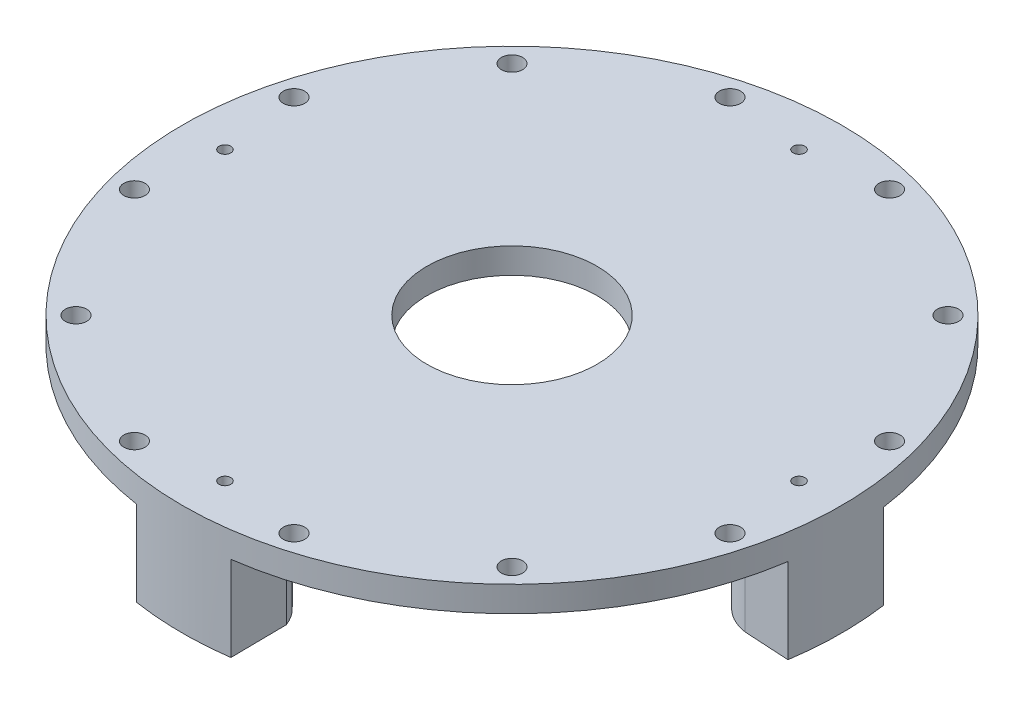
SolidWorks part; units mm, degrees
material "6061-T6 (SS)"
ref_plane "Front Plane" through (0, 0, 0) normal (0, 0, 1) x (1, 0, 0)
ref_plane "Top Plane" through (0, 0, 0) normal (0, 1, 0) x (1, 0, 0)
ref_plane "Right Plane" through (0, 0, 0) normal (1, 0, 0) x (0, 0, -1)
sketch "Sketch1" plane through (0, 0, 0) normal (0, 1, 0) x (1, 0, 0)
  circle A0 centre (0, 0) radius 98.425
  circle A1 centre (0, 0) radius 25.4
  dimension "D1" = 196.85
  dimension "D2" = 50.8
extrude "Boss-Extrude1" add sketch "Sketch1" along normal blind 7.62
sketch "Sketch2" plane through (0, 0, 0) normal (0, -1, 0) x (1, 0, 0)
  line L0 (0, 0) -> (0, 75.6548) construction
  line L1 (13.05, 85.725) -> (0.0025, 85.725) construction
  line L2 (-12.7, 85.725) -> (-1009.5225, 85.725) construction
  line L3 (0, 73.025) -> (0, 50000) construction
  line L4 (-14.0929, 83.7516) -> (-14.8752, 97.2945)
  line L6 (13.5312, 97.4904) -> (13.3337, 80.7532)
  line L13 (83.7516, 14.0929) -> (97.2945, 14.8752)
  line L14 (97.4904, -13.5312) -> (80.7532, -13.3337)
  line L15 (14.0929, -83.7516) -> (14.8752, -97.2945)
  line L16 (-13.5312, -97.4904) -> (-13.3337, -80.7532)
  line L17 (-83.7516, -14.0929) -> (-97.2945, -14.8752)
  line L18 (-97.4904, 13.5312) -> (-80.7532, 13.3337)
  arc A0 (0.1408, 73.0258) -> (0, 73.025) centre (0, 85.725) ccw construction
  circle A1 centre (0, 0) radius 98.425 construction
  arc A10 (-14.0929, 83.7516) -> (13.3337, 80.7532) centre (0, 85.725) ccw
  arc A25 (-14.8752, 97.2945) -> (13.5312, 97.4904) centre (0, 0) cw
  arc A26 (97.2945, 14.8752) -> (97.4904, -13.5312) centre (0, 0) cw
  arc A27 (83.7516, 14.0929) -> (80.7532, -13.3337) centre (85.725, 0) ccw
  arc A28 (14.8752, -97.2945) -> (-13.5312, -97.4904) centre (0, 0) cw
  arc A29 (14.0929, -83.7516) -> (-13.3337, -80.7532) centre (0, -85.725) ccw
  arc A30 (-97.2945, -14.8752) -> (-97.4904, 13.5312) centre (0, 0) cw
  arc A31 (-83.7516, -14.0929) -> (-80.7532, 13.3337) centre (-85.725, 0) ccw
  point P7 (-12.7, 85.725)
  point P8 (12.7, 85.725)
  point P9 (12.2673, 82.438)
  point P13 (0, 93.5788)
  point P17 (-12.2673, 82.438)
  point P26 (12.556, 85.725)
  point P27 (-12.6299, 85.725)
  point P28 (-12.6299, 85.725)
  point P44 (0, 0)
  point P52 (0, 0)
  dimension "D1" = 4
  dimension "D2" = 85.725
extrude "Boss-Extrude2" add sketch "Sketch2" along normal blind 25.4
sketch "Sketch4" plane through (0, 7.62, 0) normal (0, 1, 0) x (1, 0, 0)
  line L0 (0, 0) -> (23.8636, 89.0603) construction
  line L1 (0, 0) -> (0, 98.425) construction
  circle A0 centre (23.8636, 89.0603) radius 3.175
  circle A1 centre (65.1967, 65.1967) radius 3.175
  circle A2 centre (89.0603, 23.8636) radius 3.175
  circle A3 centre (89.0603, -23.8636) radius 3.175
  circle A4 centre (65.1967, -65.1967) radius 3.175
  circle A5 centre (23.8636, -89.0603) radius 3.175
  circle A6 centre (-23.8636, -89.0603) radius 3.175
  circle A7 centre (-65.1967, -65.1967) radius 3.175
  circle A8 centre (-89.0603, -23.8636) radius 3.175
  circle A9 centre (-89.0603, 23.8636) radius 3.175
  circle A10 centre (-65.1967, 65.1967) radius 3.175
  circle A11 centre (-23.8636, 89.0603) radius 3.175
  circle A12 centre (0, 0) radius 98.425 construction
  point P28 (0, 0)
  dimension "D1" = 6.35
  dimension "D3" = 12
  dimension "D2" = 92.202
  dimension "D4" = 15
sketch "Sketch5" plane through (0, -25.4, 0) normal (0, -1, 0) x (1, 0, 0)
  line L0 (200013.05, 85.725) -> (-199999.9975, 85.725) construction
  line L1 (0, 73.025) -> (0, 250000) construction
  line L2 (200013.05, 85.725) -> (-199999.9975, 85.725) construction
  line L3 (0, 73.025) -> (0, 250000) construction
  circle A0 centre (0, 85.725) radius 5.2578
  point P17 (0.7848, -0.7848)
  dimension "D1" = 10.5156
  dimension "D2" = 85.725
extrude "Cut-Extrude3" cut sketch "Sketch5" against normal blind 19.05
sketch "Sketch6" plane through (0, 7.62, 0) normal (0, 1, 0) x (1, 0, 0)
  line L0 (0, 0) -> (0, 98.425) construction
  line L1 (0, 0) -> (-25.4743, 95.0712) construction
  circle A0 centre (0, 0) radius 98.425 construction
  circle A1 centre (-23.8308, 88.9376) radius 3.175
  point P33 (0, 0)
  dimension "D2" = 6.35
  dimension "D1" = 15
  dimension "D3" = 92.075
extrude "Cut-Extrude4" cut sketch "Sketch6" against normal blind 12.7
extrude "Cut-Extrude2" [suppressed] cut sketch "Sketch4" against normal blind 12.7
pattern_circular "CirPattern1" count 12 over 360 about axis through (0, 7.62, 0) along (0, -1, 0) of "Cut-Extrude4"
pattern_circular "CirPattern2" count 4 over 360 about axis through (0, 7.62, 0) along (0, -1, 0) of "Cut-Extrude3"
ref_plane "Plane1" through (0, 7.62, 0) normal (0, 1, 0) x (1, 0, 0)
sketch "Sketch8" plane through (0, 7.62, 0) normal (0, 1, 0) x (1, 0, 0)
  circle A0 centre (0, 85.725) radius 1.7526
  dimension "D1" = 3.5052
extrude "Cut-Extrude6" cut sketch "Sketch8" against normal through all
pattern_circular "CirPattern3" count 4 over 360 about axis through (0, 7.62, 0) along (0, -1, 0) of "Cut-Extrude6" reverse direction yes
sketch "Sketch9" plane through (0, 7.62, 0) normal (0, 1, 0) x (1, 0, 0)
  circle A0 centre (0, 0) radius 98.425 construction
  point P0 (0, 85.725)
  point P1 (0, 98.425)
